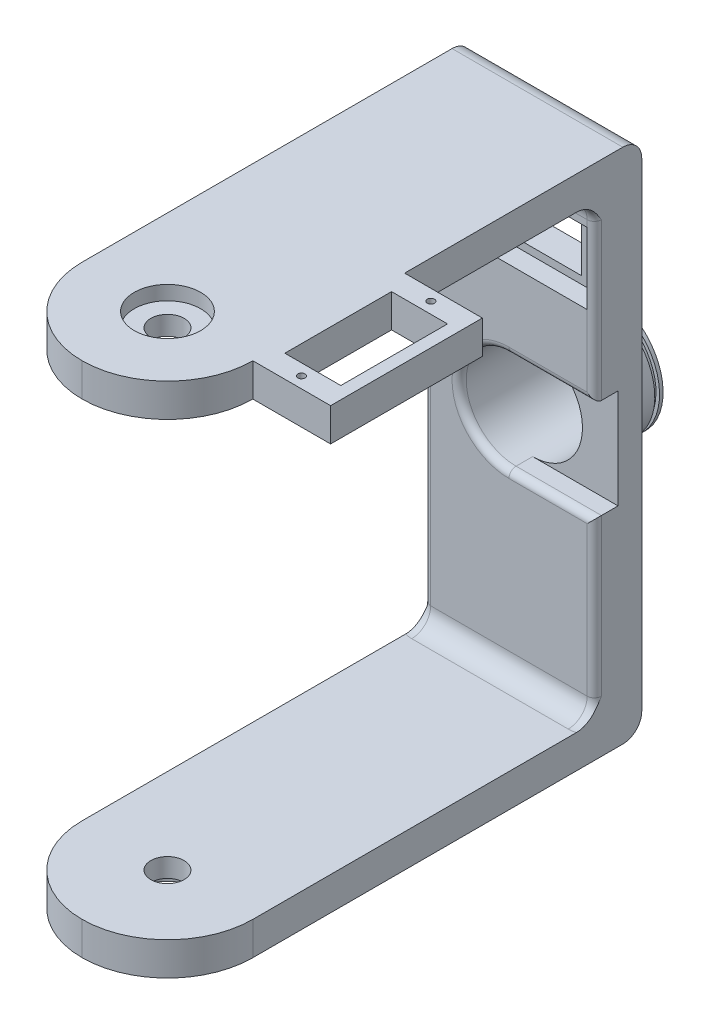
SolidWorks part; units mm, degrees
ref_plane "Front Plane" through (0, 0, 0) normal (1, 0, 0) x (0, 1, 0)
ref_plane "Top Plane" through (0, 0, 0) normal (0, 0, 1) x (0, 1, 0)
ref_plane "Right Plane" through (0, 0, 0) normal (0, 1, 0) x (-1, 0, 0)
sketch "Sketch1" plane through (0, 0, 0) normal (0, 0, 1) x (0, 1, 0)
  line L1 (-54.5, -18) -> (54.5, -18)
  line L2 (-54.5, -18) -> (-54.5, 18)
  line L3 (-54.5, 18) -> (54.5, 18)
  line L4 (54.5, -18) -> (54.5, 18)
  line L5 (-54.5, -18) -> (54.5, 18) construction
  line L6 (-54.5, 18) -> (54.5, -18) construction
  point P0 (0, 0)
  dimension "D1" = 109
  dimension "D2" = 36
extrude "Boss-Extrude1" add sketch "Sketch1" along normal blind 10
sketch "Sketch2" plane through (0, 0, 10) normal (0, 0, 1) x (1, 0, 0)
  line L0 (18, -54.5) -> (18, 54.5) construction
  line L1 (-18, 54.5) -> (18, 54.5)
  line L2 (-18, 54.5) -> (-18, 47.5)
  line L3 (-18, 47.5) -> (18, 47.5)
  line L4 (18, 54.5) -> (18, 47.5)
  line L6 (-18, -54.5) -> (18, -54.5)
  line L7 (-18, -54.5) -> (-18, -47.5)
  line L8 (-18, -47.5) -> (18, -47.5)
  line L9 (18, -54.5) -> (18, -47.5)
  dimension "D1" = 7
extrude "Boss-Extrude2" add sketch "Sketch2" along normal blind 90
sketch "Sketch3" plane through (0, -54.5, 0) normal (0, -1, 0) x (1, 0, 0)
  line L0 (-18, 82) -> (18, 82) construction
  line L1 (-18, 100) -> (-18, 0) construction
  line L2 (18, 100) -> (18, 0) construction
  line L3 (-18, 100) -> (18, 100) construction
  circle A0 centre (0, 82) radius 3.5
  dimension "D2" = 7
  dimension "D1" = 18
extrude "Cut-Extrude1" cut sketch "Sketch3" against normal through all both and the other way through all
sketch "Sketch4" plane through (0, -54.5, 0) normal (0, -1, 0) x (1, 0, 0)
  circle A0 centre (0, 82) radius 7
  dimension "D1" = 14
extrude "Cut-Extrude2" cut sketch "Sketch4" against normal blind 3 and the other way through all
sketch "Sketch5" plane through (0, 54.5, 0) normal (0, 1, 0) x (-1, 0, 0)
  circle A0 centre (0, 82) radius 7
  dimension "D1" = 14
extrude "Cut-Extrude3" cut sketch "Sketch5" against normal blind 3
fillet "Fillet1" radius 18 4 edges at (18, -51, 100) (-18, -51, 100) (18, 51, 100) (-18, 51, 100)
sketch "Sketch6" plane through (0, 0, 0) normal (0, 0, -1) x (1, 0, 0)
  circle A0 centre (0, 0) radius 12.5
  dimension "D1" = 25
extrude "Boss-Extrude3" add sketch "Sketch6" along normal blind 10
sketch "Sketch15" plane through (0, 0, 0) normal (0, 0, -1) x (1, 0, 0)
  circle A0 centre (0, 0) radius 13.75
  dimension "D1" = 27.5
extrude "Boss-Extrude5" add sketch "Sketch15" along normal blind 4.25
sketch "Sketch7" plane through (0, 0, -10) normal (0, 0, -1) x (1, 0, 0)
  circle A0 centre (0, 0) radius 10.5
  dimension "D1" = 21
extrude "Cut-Extrude4" cut sketch "Sketch7" against normal through all
sketch "Sketch9" plane through (0, 0, 10) normal (0, 0, 1) x (1, 0, 0)
  line L0 (0, 0) -> (0, 47.5) construction
  line L1 (0, 34.5887) -> (18, 34.5887) construction
  line L2 (-11.25, 28.6887) -> (11.25, 28.6887)
  line L3 (-11.25, 28.6887) -> (-11.25, 40.4887)
  line L4 (-11.25, 40.4887) -> (11.25, 40.4887)
  line L5 (11.25, 28.6887) -> (11.25, 40.4887)
  line L6 (-11.25, 28.6887) -> (11.25, 40.4887) construction
  line L7 (-11.25, 40.4887) -> (11.25, 28.6887) construction
  line L8 (18, -47.5) -> (18, 47.5) construction
  line L9 (0, 34.5887) -> (-18, 34.5887) construction
  line L10 (-18, 47.5) -> (-18, -47.5) construction
  circle A1 centre (-13.65, 34.5887) radius 0.75
  circle A2 centre (13.65, 34.5887) radius 0.75
  circle A3 centre (-5.35, 34.5887) radius 5.9 construction
  point P4 (0, 34.5887)
  dimension "D5" = 1.5
  dimension "D1" = 22.5
  dimension "D2" = 11.8
  dimension "D3" = 35
  dimension "D4" = 13.65
  dimension "D6" = 13.65
extrude "Cut-Extrude5" cut sketch "Sketch9" against normal through all
sketch "Sketch10" plane through (0, 0, 10) normal (0, 0, 1) x (1, 0, 0)
  line L0 (-11.25, 34.5887) -> (11.25, 34.5887) construction
  line L1 (-11.25, 40.4887) -> (-11.25, 28.6887) construction
  line L2 (11.25, 28.6887) -> (11.25, 40.4887) construction
  line L4 (-16.5, 27.0887) -> (16.5, 27.0887)
  line L5 (-16.5, 27.0887) -> (-16.5, 42.0887)
  line L6 (-16.5, 42.0887) -> (16.5, 42.0887)
  line L7 (16.5, 27.0887) -> (16.5, 42.0887)
  line L8 (-16.5, 27.0887) -> (16.5, 42.0887) construction
  line L9 (-16.5, 42.0887) -> (16.5, 27.0887) construction
  point P6 (0, 34.5887)
  dimension "D1" = 15
  dimension "D2" = 33
extrude "Cut-Extrude6" cut sketch "Sketch10" against normal offset from surface (4 mm away) 6 up to face at (12.9, 34.5887, 0)
sketch "Sketch11" plane through (0, 54.5, 0) normal (0, 1, 0) x (-1, 0, 0)
  line L0 (-18, 82) -> (0, 82) construction
  line L1 (-25.8955, 82) -> (-25.8955, 50) construction
  line L2 (-17.3955, 82) -> (-34.3955, 82)
  line L3 (-17.3955, 82) -> (-17.3955, 50)
  line L4 (-17.3955, 50) -> (-34.3955, 50)
  line L5 (-34.3955, 82) -> (-34.3955, 50)
  line L6 (-34.3955, 66) -> (-25.8955, 66) construction
  line L7 (-31.7955, 54.75) -> (-19.9955, 54.75) construction
  line L8 (-31.7955, 54.75) -> (-31.7955, 77.25) construction
  line L9 (-31.7955, 77.25) -> (-19.9955, 77.25) construction
  line L10 (-19.9955, 54.75) -> (-19.9955, 77.25) construction
  line L11 (-31.7955, 54.75) -> (-19.9955, 77.25) construction
  line L12 (-31.7955, 77.25) -> (-19.9955, 54.75) construction
  circle A1 centre (-25.8955, 71.35) radius 5.9 construction
  point P10 (-25.8955, 66)
  dimension "D1" = 17
  dimension "D2" = 32
  dimension "D3" = 11.8
  dimension "D4" = 22.5
  dimension "D5" = 28
extrude "Boss-Extrude4" add sketch "Sketch11" against normal blind 7
sketch "Sketch12" plane through (0, 54.5, 0) normal (0, 1, 0) x (-1, 0, 0)
  line L0 (-34.3955, 66) -> (18, 66) construction
  line L1 (-34.3955, 82) -> (-34.3955, 50) construction
  line L2 (18, 82) -> (18, 0) construction
  line L3 (-18, 82) -> (-34.3955, 82) construction
  line L4 (-34.3955, 50) -> (-17.3955, 50) construction
  line L5 (-34.3955, 50) -> (-34.3955, 82) construction
  line L6 (-34.3955, 82) -> (-17.3955, 82) construction
  line L7 (-17.3955, 50) -> (-17.3955, 82) construction
  line L8 (-34.3955, 50) -> (-17.3955, 82) construction
  line L9 (-34.3955, 82) -> (-17.3955, 50) construction
  line L10 (-25.8955, 82) -> (-25.8955, 66) construction
  line L11 (-31.7955, 54.75) -> (-19.9955, 54.75)
  line L12 (-31.7955, 54.75) -> (-31.7955, 77.25)
  line L13 (-31.7955, 77.25) -> (-19.9955, 77.25)
  line L14 (-19.9955, 54.75) -> (-19.9955, 77.25)
  line L15 (-31.7955, 54.75) -> (-19.9955, 77.25) construction
  line L16 (-31.7955, 77.25) -> (-19.9955, 54.75) construction
  circle A0 centre (-25.8955, 79.65) radius 0.75
  circle A1 centre (-25.8955, 52.35) radius 0.75
  point P6 (-25.8955, 66)
  point P13 (-25.8955, 66)
  dimension "D4" = 1.5
  dimension "D1" = 17
  dimension "D2" = 11.8
  dimension "D3" = 22.5
  dimension "D5" = 13.65
extrude "Cut-Extrude7" cut sketch "Sketch12" against normal up to next
sketch "Sketch13" plane through (0, 0, 10) normal (0, 0, 1) x (1, 0, 0)
  line L1 (18, -10.5) -> (18, 10.5)
  line L4 (0, 0) -> (18, 0) construction
  line L5 (18, -47.5) -> (18, 47.5) construction
  line L6 (18, 10.5) -> (0, 10.5)
  line L7 (0, -10.5) -> (18, -10.5)
  circle A0 centre (0, 0) radius 10.5 construction
  arc A1 (0, 10.5) -> (0, -10.5) centre (0, 0) cw
extrude "Cut-Extrude8" cut sketch "Sketch13" against normal blind 5
fillet "Fillet3" radius 1.5 6 edges at (9, -10.5, 10) (-10.5, 0, 10) (9, 10.5, 10) (-18, 0, 10) (18, -29, 10) (18, 29, 10)
fillet "Fillet4" radius 4 8 edges at (17.5607, -47.5, 9.5607) (-17.5607, -47.5, 9.5607) (-17.5607, 47.5, 9.5607) (17.5607, 47.5, 9.5607) (0, -47.5, 10) (0, 47.5, 10) (0, -54.5, 0) (0, 54.5, 0)
sketch "Sketch14" plane through (0, 0, 0) normal (1, 0, 0) x (0, 1, 0)
  line L0 (0, -10) -> (0, 10) construction
  line L1 (-10.5, -10) -> (10.5, -10) construction
  line L2 (12, 10) -> (-12, 10) construction
  line L3 (-12.5, -10) -> (12.5, -10) construction
  line L4 (-13, -9.25) -> (-11.75, -9.25)
  line L5 (-13, -9.25) -> (-13, -8.25)
  line L6 (-13, -8.25) -> (-11.75, -8.25)
  line L7 (-11.75, -9.25) -> (-11.75, -8.25)
  dimension "D1" = 1
  dimension "D2" = 13
  dimension "D3" = 11.75
  dimension "D4" = 0.75
revolve "Cut-Revolve1" cut sketch "Sketch14" angle 360 about L0
fillet "Fillet5" radius 1 1 edges at (-13.75, 0, 0)
